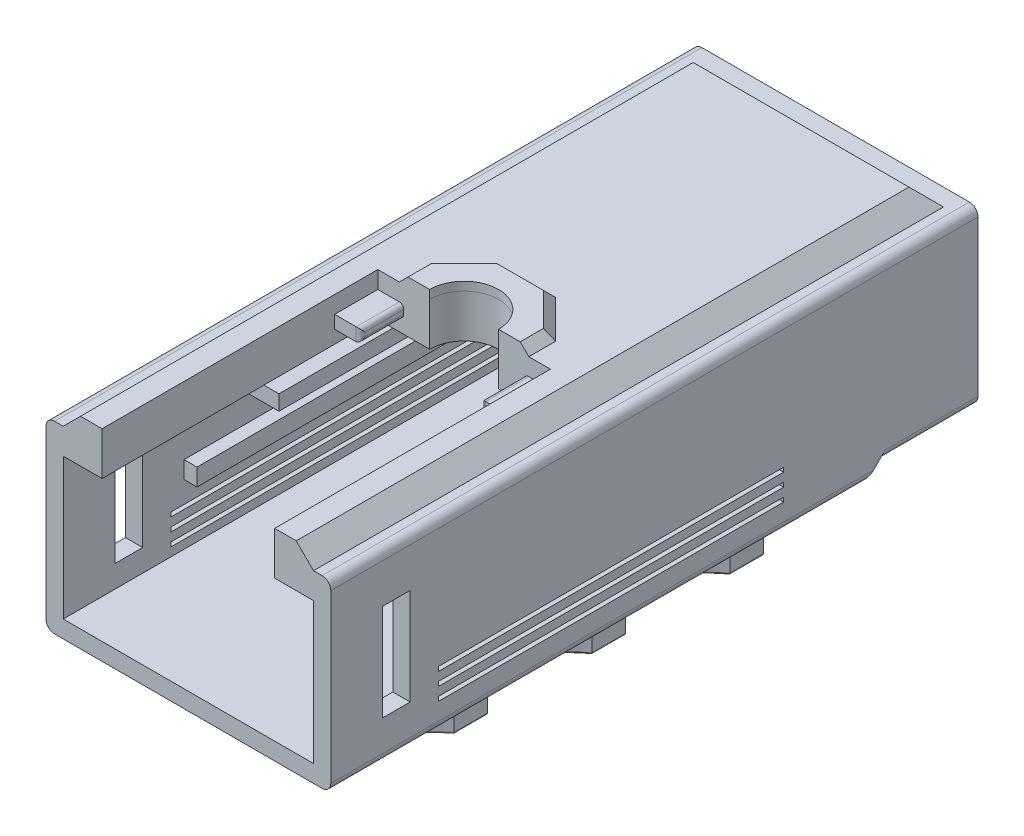
SolidWorks part; units mm, degrees
ref_plane "Front Plane" through (0, 0, 0) normal (0, 0, 1) x (1, 0, 0)
ref_plane "Top Plane" through (0, 0, 0) normal (0, 1, 0) x (1, 0, 0)
ref_plane "Right Plane" through (0, 0, 0) normal (1, 0, 0) x (0, 0, -1)
sketch "Sketch1" plane through (0, 0, 0) normal (0, 0, 1) x (1, 0, 0)
  line L1 (-16.5, 10) -> (16.5, 10)
  line L2 (-16.5, 10) -> (-16.5, -10)
  line L3 (-16.5, -10) -> (16.5, -10)
  line L4 (16.5, 10) -> (16.5, -10)
  line L5 (-16.5, 10) -> (16.5, -10) construction
  line L6 (-16.5, -10) -> (16.5, 10) construction
  point P0 (0, 0)
  dimension "D1" = 33
  dimension "D2" = 20
extrude "Boss-Extrude1" add sketch "Sketch1" along normal blind 70
sketch "Sketch2" plane through (0, 0, 0) normal (0, 0, -1) x (-1, 0, 0)
  line L1 (-16.5, 10) -> (16.5, 10)
  line L2 (-16.5, 10) -> (-16.5, -10)
  line L3 (-16.5, -10) -> (16.5, -10)
  line L4 (16.5, 10) -> (16.5, -10)
  line L5 (-14.5, 7) -> (14.5, 7)
  line L6 (-14.5, 7) -> (-14.5, -7)
  line L7 (-14.5, -7) -> (14.5, -7)
  line L8 (14.5, 7) -> (14.5, -7)
  dimension "D1" = 3
  dimension "D2" = 2
  dimension "D3" = 3
  dimension "D4" = 2
extrude "Cut-Extrude1" cut sketch "Sketch2" against normal blind 9 contours L8 L5 L6 L7 region at (0, 0, 0)
sketch "Sketch3" plane through (0, 0, 70) normal (0, 0, 1) x (1, 0, 0)
  line L1 (-16.5, 10) -> (16.5, 10)
  line L2 (-16.5, 10) -> (-16.5, -10)
  line L3 (-16.5, -10) -> (16.5, -10)
  line L4 (16.5, 10) -> (16.5, -10)
  line L5 (-14.5, 8) -> (14.5, 8)
  line L6 (-14.5, 8) -> (-14.5, -8)
  line L7 (-14.5, -8) -> (14.5, -8)
  line L8 (14.5, 8) -> (14.5, -8)
  dimension "D1" = 2
  dimension "D2" = 2
  dimension "D3" = 2
  dimension "D4" = 2
extrude "Cut-Extrude2" cut sketch "Sketch3" against normal blind 59 contours L8 L5 L6 L7 region at (0, 0, 70)
sketch "Sketch5" plane through (0, 0, 9) normal (0, 0, -1) x (-1, 0, 0)
  line L0 (-14.5, 7) -> (-8.5, 7)
  line L1 (-8.5, 7) -> (-7.5, 7)
  line L2 (-14.5, 7) -> (14.5, 7) construction
  line L3 (-7.5, 7) -> (-0.5, 7)
  line L4 (-14.5, 7) -> (-14.5, 1)
  line L5 (-0.5, 7) -> (0.5, 7)
  line L6 (-14.5, 7) -> (14.5, 7) construction
  line L7 (0.5, 7) -> (7.5, 7)
  line L8 (7.5, 7) -> (8.5, 7)
  line L9 (8.5, 7) -> (14.5, 7)
  line L11 (-14.5, 7) -> (-14.5, -7) construction
  line L12 (14.5, 7) -> (14.5, -7) construction
  line L13 (8.5, -7) -> (14.5, -7)
  line L14 (7.5, -7) -> (8.5, -7)
  line L15 (0.5, -7) -> (7.5, -7)
  line L16 (-0.5, -7) -> (0.5, -7)
  line L17 (-7.5, -7) -> (-0.5, -7)
  line L18 (-8.5, -7) -> (-7.5, -7)
  line L19 (-14.5, -7) -> (-8.5, -7)
  line L20 (-14.5, 7) -> (-14.5, -7) construction
  line L21 (-14.5, -7) -> (-14.5, 0)
  line L22 (-14.5, 1) -> (-14.5, 0)
  line L23 (14.5, -7) -> (14.5, 0)
  line L24 (14.5, 7) -> (14.5, 1)
  line L25 (14.5, 1) -> (14.5, 0)
  line L26 (14.5, 1) -> (14.5, 0)
  line L27 (-8.5, 7) -> (-8.5, 5.2)
  line L28 (-8.5, 5.2) -> (-7.5, 5.2)
  line L29 (-7.5, 5.2) -> (-7.5, 7)
  line L30 (-14.5, 1) -> (-12.7, 1)
  line L31 (-12.7, 1) -> (-12.7, 0)
  line L32 (-12.7, 0) -> (-14.5, 0)
  line L33 (-0.5, 7) -> (-0.5, 1)
  line L34 (0.5, -7) -> (0.5, 0)
  line L35 (14.5, 1) -> (12.7, 1)
  line L36 (12.7, 1) -> (12.7, 0)
  line L37 (12.7, 0) -> (14.5, 0)
  line L38 (8.5, -7) -> (8.5, -4.2)
  line L39 (8.5, -4.2) -> (7.5, -4.2)
  line L40 (7.5, -4.2) -> (7.5, -7)
  line L41 (-7.5, -7) -> (-7.5, -4.2)
  line L42 (-7.5, -4.2) -> (-8.5, -4.2)
  line L43 (-8.5, -4.2) -> (-8.5, -7)
  line L44 (-0.5, 1) -> (-3.2992, 1)
  line L45 (-3.2992, 1) -> (-3.2992, 0)
  line L46 (-3.2992, 0) -> (-0.5, 0)
  line L47 (0.5, 1) -> (3.3, 1)
  line L48 (3.3, 1) -> (3.3, 0)
  line L49 (3.3, 0) -> (0.5, 0)
  line L50 (7.5, 7) -> (7.5, 5.2)
  line L51 (7.5, 5.2) -> (8.5, 5.2)
  line L52 (8.5, 5.2) -> (8.5, 7)
  line L53 (-0.5, 1) -> (0.5, 1)
  line L54 (-0.5, 0) -> (0.5, 0)
  line L55 (-0.5, 0) -> (-0.5, -7)
  line L56 (0.5, 1) -> (0.5, 7)
  line M8 (14.5, -7) -> (14.5, 7)
  line M9 (14.5, 7) -> (-14.5, 7)
  line M10 (-14.5, 7) -> (-14.5, -7)
  line M11 (-14.5, -7) -> (14.5, -7)
extrude "Boss-Extrude2" add sketch "Sketch5" along normal blind 9 contours L51 L52 L50 M9 | L36 L37 L35 M8 | L39 L40 L38 M11 | L28 L29 L27 M9 | L32 L31 L30 M10 | L42 L43 L41 M11 | L49 L48 L47 L34 region at (8, 6.1, 9) region at (13.6, 0.5, 9) region at (-0.0004, 0.5, 9) region at (8, -5.6, 9) region at (-8, 6.1, 9) region at (-13.6, 0.5, 9) region at (-8, -5.6, 9)
extrude "Boss-Extrude3" add sketch "Sketch5<4>" along normal blind 8 contours L54 L55 L34 M11 | L53 L56 L33 M9 region at (0, 4, 9) region at (0, -3.5, 9)
sketch "Sketch5<4>" plane through (0, 0, 9) normal (0, 0, -1) x (-1, 0, 0) same geometry as "Sketch5"
fillet "Fillet1" radius 1 8 edges at (3.2992, 0.5, 0) (-3.3, 0.5, 0) (-8, 5.2, 0) (-12.7, 0.5, 0) (-8, -4.2, 0) (8, -4.2, 0) (12.7, 0.5, 0) (8, 5.2, 0)
sketch "Sketch6" plane through (0, 0, 70) normal (0, 0, 1) x (1, 0, 0)
  line L1 (-16.5, 10) -> (16.5, 10)
  line L2 (-16.5, 10) -> (-16.5, -10)
  line L3 (-16.5, -10) -> (16.5, -10)
  line L4 (16.5, 10) -> (16.5, -10)
  line L5 (-14.5, 8) -> (14.5, 8)
  line L6 (-14.5, 8) -> (-14.5, -8)
  line L7 (-14.5, -8) -> (14.5, -8)
  line L8 (14.5, 8) -> (14.5, -8)
extrude "Cut-Extrude3" cut sketch "Sketch6" against normal blind 19
sketch "Sketch9" plane through (0, 10, 0) normal (0, 1, 0) x (1, 0, 0)
  line L10 (-10, -43.05) -> (-10, -51)
  line L11 (-10, -51) -> (10, -51)
  line L12 (10, -51) -> (10, -43.05)
  line L13 (-4, -43.05) -> (-10, -43.05)
  line L14 (4, -43.05) -> (10, -43.05)
  arc A2 (4, -43.05) -> (-4, -43.05) centre (0, -43.05) ccw
extrude "Cut-Extrude5" cut sketch "Sketch9" against normal blind 2
sketch "Sketch10" plane through (0, 10, 0) normal (0, 1, 0) x (1, 0, 0)
  line L0 (16.5, -51) -> (16.5, 0) construction
  line L1 (-14.5, -2) -> (14.5, -2)
  line L2 (-14.5, -2) -> (-14.5, -42.9994)
  line L4 (14.5, -2) -> (14.5, -42.9994)
  line L5 (-16.5, -51) -> (-16.5, 0) construction
  line L7 (-14.5, -42.9994) -> (-14.5, -51)
  line L8 (-10, -51) -> (-16.5, -51) construction
  line L9 (-14.5, -51) -> (-10, -51)
  line L10 (-10, -51) -> (-10, -43.05)
  line L11 (-10, -43.05) -> (10, -43.05)
  line L12 (10, -43.05) -> (10, -51)
  line L13 (10, -51) -> (14.5, -51)
  line L14 (16.5, -51) -> (10, -51) construction
  line L15 (14.5, -51) -> (14.5, -42.9994)
  arc A0 (4, -42.9994) -> (-4, -42.9994) centre (0, -42.9994) ccw
  dimension "D4" = 8
  dimension "D1" = 2
  dimension "D2" = 2
  dimension "D3" = 2
extrude "Boss-Extrude4" add sketch "Sketch10" along normal blind 2 contours L15 L4 L1 L2 L7 region at (0, 10, 23.5597)
sketch "Sketch11" plane through (0, 8, 0) normal (0, -1, 0) x (1, 0, 0)
  line L0 (14.5, 43.05) -> (14.5, 51)
  line L1 (14.5, 51) -> (10, 51)
  line L2 (0, 31.55) -> (-14.5, 31.55)
  line L4 (-4, 43.05) -> (-10, 43.05)
  line L5 (-14.5, 31.55) -> (-14.5, 43.05)
  line L6 (0, 31.55) -> (14.5, 31.55)
  line L8 (4, 43.05) -> (10, 43.05)
  line L9 (14.5, 31.55) -> (14.5, 43.05)
  line L10 (14.5, 51) -> (10, 51) construction
  line L11 (10, 51) -> (10, 43.05)
  line L12 (-10, 43.05) -> (-10, 51)
  line L13 (-10, 51) -> (-14.5, 51)
  line L14 (-14.5, 51) -> (-14.5, 43.05)
  arc A1 (-4, 43.05) -> (4, 43.05) centre (0, 43.05) ccw
  dimension "D4" = 8
  dimension "D1" = 11.5
  dimension "D2" = 14.5
  dimension "D3" = 14.5
extrude "Boss-Extrude5" add sketch "Sketch11" along normal blind 1
sketch "Sketch13" plane through (14.5, 0, 0) normal (-1, 0, 0) x (0, 0, 1)
  line L1 (31.55, 4.75) -> (51, 4.75)
  line L2 (51, -8) -> (51, 7) construction
  line L7 (51, 4.75) -> (31.55, 4.75)
  line L8 (51, 4.75) -> (51, 3)
  line L9 (51, 3) -> (31.55, 3)
  line L10 (31.55, 4.75) -> (31.55, 3)
  line L11 (51, 4.75) -> (51, 7)
  line L12 (51, 7) -> (31.55, 7)
  line L13 (31.55, 7) -> (31.55, 4.75)
  line M4 (51, 7) -> (31.55, 7)
  line M9 (51, -8) -> (51, 7)
  dimension "D3" = 1.75
extrude "Boss-Extrude6" add sketch "Sketch13" along normal blind 6 contours L1 L10 L9 M9 region at (14.5, 3.875, 41.275)
extrude "Boss-Extrude7" add sketch "Sketch13<5>" along normal blind 4.5 contours L13 L1 M4 M9 region at (14.5, 5.875, 41.275)
sketch "Sketch13<5>" plane through (14.5, 0, 0) normal (-1, 0, 0) x (0, 0, 1) same geometry as "Sketch13"
sketch "Sketch14" plane through (-14.5, 0, 0) normal (1, 0, 0) x (0, 0, -1)
  line L6 (-31.55, 7) -> (-51, 7)
  line L7 (-51, 7) -> (-51, 4.75)
  line L8 (-51, 7) -> (-51, -8) construction
  line L9 (-51, 4.75) -> (-31.55, 4.75)
  line L10 (-31.55, 4.75) -> (-31.55, 7)
  line L11 (-31.55, 4.75) -> (-31.55, 3)
  line L12 (-31.55, 3) -> (-51, 3)
  line L13 (-51, 3) -> (-51, 4.75)
  line M5 (-31.55, 7) -> (-51, 7)
  line M6 (-51, 7) -> (-51, -8)
  dimension "D1" = 2.25
  dimension "D2" = 1.75
extrude "Boss-Extrude8" add sketch "Sketch14" along normal blind 4 contours L12 L11 L9 M6 region at (-14.5, 3.875, 41.275)
extrude "Boss-Extrude9" add sketch "Sketch14<3>" along normal blind 1.75 contours L9 L10 M5 M6 region at (-14.5, 5.875, 41.275)
sketch "Sketch14<3>" plane through (-14.5, 0, 0) normal (1, 0, 0) x (0, 0, -1) same geometry as "Sketch14"
sketch "Sketch18" plane through (14.5, 0, 0) normal (-1, 0, 0) x (0, 0, 1)
  line L4 (51, -8) -> (51, 3) construction
  line L8 (51, -0.35) -> (51, -2.35)
  line L11 (51, -0.35) -> (21, -0.35)
  line L12 (51, -0.35) -> (51, -2.35)
  line L13 (51, -2.35) -> (21, -2.35)
  line L14 (21, -0.35) -> (21, -2.35)
  line M9 (51, -8) -> (51, 3)
  dimension "D1" = 30
  dimension "D2" = 2
extrude "Boss-Extrude11" add sketch "Sketch18" along normal blind 1.5 contours L11 L14 L13 M9 region at (14.5, -1.35, 36)
sketch "Sketch19" plane through (-14.5, 0, 0) normal (1, 0, 0) x (0, 0, -1)
  line L0 (-51, 3) -> (-51, -0.35)
  line L1 (-51, 3) -> (-51, -8) construction
  line L3 (-51, -0.35) -> (-21, -0.35)
  line L4 (-51, -0.35) -> (-51, -2.35)
  line L5 (-51, -2.35) -> (-21, -2.35)
  line L6 (-21, -0.35) -> (-21, -2.35)
  line M7 (-51, 3) -> (-51, -8)
  dimension "D1" = 3.35
  dimension "D2" = 2
  dimension "D3" = 30
extrude "Boss-Extrude12" add sketch "Sketch19" along normal blind 1.5 contours L6 L3 L5 M7 region at (-14.5, -1.35, 36)
sketch "Sketch20" plane through (0, 0, 51) normal (0, 0, 1) x (1, 0, 0)
  line L1 (-14.5, 3) -> (14.5, 3)
  line L2 (-14.5, 3) -> (-14.5, -0.35)
  line L3 (-14.5, -0.35) -> (14.5, -0.35)
  line L4 (14.5, 3) -> (14.5, -0.35)
extrude "Boss-Extrude14" add sketch "Sketch20" against normal blind 2 from offset 30 separate body offset against normal yes
sketch "Sketch21" plane through (-14.5, 0, 0) normal (1, 0, 0) x (0, 0, -1)
  circle A0 centre (-16, -3) radius 2.5
  dimension "D3" = 5
extrude "Cut-Extrude7" cut sketch "Sketch21" against normal through all
sketch "Sketch23" plane through (0, 0, 51) normal (0, 0, 1) x (1, 0, 0)
  line L1 (10, 4.75) -> (-12.75, 4.75)
  line L2 (10, 4.75) -> (10, 7)
  line L3 (10, 7) -> (-12.75, 7)
  line L4 (-12.75, 4.75) -> (-12.75, 7)
extrude "Boss-Extrude15" add sketch "Sketch23" along normal blind 2 from offset 19.95 separate body offset against normal yes
sketch "Sketch24" plane through (0, -8, 0) normal (0, 1, 0) x (1, 0, 0)
  line L0 (-14.5, -2) -> (-14.5, -51) construction
  line L1 (-14.5, -11.1047) -> (14.5, -11.1047)
  line L2 (-14.5, -11.1047) -> (-14.5, -51)
  line L3 (-14.5, -51) -> (14.5, -51)
  line L4 (14.5, -11.1047) -> (14.5, -51)
extrude "Cut-Extrude8" cut sketch "Sketch24" against normal through all
sketch "Sketch25" plane through (14.5, 0, 0) normal (-1, 0, 0) x (0, 0, 1)
  line L1 (51, -10) -> (51, -2.35) construction
  line L2 (51, -9.35) -> (11.1047, -9.35)
  line L3 (11.1047, -10) -> (11.1047, -8) construction
  line L6 (51, -9.35) -> (51, -10)
  line L7 (51, -10) -> (11.1047, -10)
  line L8 (11.1047, -10) -> (11.1047, -9.35)
extrude "Cut-Extrude9" cut sketch "Sketch25" against normal through all
sketch "Sketch26" plane through (-14.5, 0, 0) normal (1, 0, 0) x (0, 0, -1)
  line L1 (-51, -2.35) -> (-51, -10) construction
  line L2 (-11.1047, -10) -> (-11.1047, -8) construction
  line L3 (-51, -9.35) -> (-11.1047, -9.35)
  line L4 (-51, -9.35) -> (-51, -10)
  line L5 (-51, -10) -> (-11.1047, -10)
  line L6 (-11.1047, -9.35) -> (-11.1047, -10)
  line L7 (-11.1047, -10) -> (-51, -10) construction
extrude "Cut-Extrude10" cut sketch "Sketch26" against normal through all
sketch "Sketch27" plane through (0, -9.35, 0) normal (0, -1, 0) x (1, 0, 0)
  line L1 (-16.5, 51) -> (16.5, 51)
  line L2 (-16.5, 51) -> (-16.5, 11.1047)
  line L3 (-16.5, 11.1047) -> (16.5, 11.1047)
  line L4 (16.5, 51) -> (16.5, 11.1047)
extrude "Boss-Extrude16" add sketch "Sketch27" along normal blind 2
sketch "Sketch31" plane through (0, 0, 51) normal (0, 0, 1) x (1, 0, 0)
  line L7 (13.5, -0.35) -> (13, -0.35)
  line L9 (13, -0.35) -> (13, -2.35)
  line L14 (13, -2.35) -> (13.5, -2.3419)
  line L17 (14.5, -0.35) -> (13.5, -0.35)
  line L18 (13, -0.35) -> (14.5, -0.35) construction
  line L20 (13.5, -2.3419) -> (14.5, -2.35)
  line L21 (13, -2.35) -> (14.5, -2.35) construction
  line L22 (14.5, -9.35) -> (14.5, -2.35) construction
  line L26 (-14.5, -2.35) -> (-13, -2.35)
  line L27 (-13, -2.35) -> (-14.5, -2.35) construction
  line L28 (-13, -2.35) -> (-13, -0.35)
  line L29 (-13, -0.35) -> (-13, -2.35) construction
  line L30 (-13, -0.35) -> (-14.5, -0.35)
  line L44 (14.5, -0.35) -> (14.5, -2.35)
  line L45 (-14.5, -0.35) -> (-14.5, -2.35)
  line M4 (-14.5, -2.35) -> (-13, -2.35)
  line M5 (-13, -2.35) -> (-13, -0.35)
  line M6 (-13, -0.35) -> (-14.5, -0.35)
  line M28 (14.5, -0.35) -> (13, -0.35)
  line M29 (13, -0.35) -> (13, -2.35)
extrude "Boss-Extrude18" add sketch "Sketch31" along normal blind 10 contours L45 M6 M4 M5 | L44 L20 M28 M29 region at (13.7502, -1.348, 51) region at (-13.75, -1.35, 51)
sketch "Sketch35" plane through (0, 0, 51) normal (0, 0, 1) x (1, 0, 0)
  line L1 (8.5, 3) -> (14.5, 3) construction
  line L2 (10, 3) -> (8.5, 3)
  line L3 (8.5, 3) -> (8.5, 4.75)
  line L4 (8.5, 3) -> (8.5, 4.75) construction
  line L5 (8.5, 4.75) -> (10, 4.75)
  line L6 (-12.75, 4.75) -> (-10.5, 4.75)
  line L7 (-10.5, 4.75) -> (-12.75, 4.75) construction
  line L8 (-10.5, 4.75) -> (-10.5, 3)
  line L10 (-10.5, 3) -> (-14.5, 3) construction
  line L11 (-12.75, 3) -> (-10.5, 3)
  line L12 (-14.5, 3) -> (-14.5, 4.75)
  line L14 (-12.75, 3) -> (-14.5, 3)
  line L15 (-12.75, 7) -> (-14.5, 7)
  line L16 (-14.5, 7) -> (-14.5, 4.75)
  line L17 (-12.75, 7) -> (-12.75, 4.75)
  line L18 (14.5, 3) -> (10, 3)
  line L19 (14.5, -0.35) -> (14.5, 3) construction
  line L20 (14.5, 3) -> (14.5, 4.75)
  line L22 (14.5, 4.75) -> (14.5, 7)
  line L23 (14.5, 7) -> (10, 7)
  line L24 (10, 4.75) -> (10, 12) construction
  line L25 (10, 7) -> (10, 4.75)
extrude "Boss-Extrude19" add sketch "Sketch35" along normal blind 3
sketch "Sketch36" plane through (0, 0, 51) normal (0, 0, 1) x (1, 0, 0)
  line L0 (-10, 12) -> (-14.5, 12)
  line L1 (-14.5, 12) -> (-10, 12) construction
  line L2 (-14.5, 12) -> (-14.5, 10) construction
  line L3 (-14.5, 12) -> (-14.5, 10)
  line L4 (-14.5, 10) -> (-16.5, 10)
  line L5 (-16.5, 10) -> (-16.5, -11.35)
  line L6 (-16.5, -11.35) -> (16.5, -11.35)
  line L7 (16.5, -11.35) -> (16.5, 10)
  line L8 (16.5, 10) -> (14.5, 10)
  line L9 (14.5, 10) -> (14.5, 12)
  line L10 (14.5, 12) -> (10, 12)
  line L11 (10, 12) -> (14.5, 12) construction
  line L14 (14.5, 3) -> (14.5, -9.35)
  line L15 (14.5, -9.35) -> (-14.5, -9.35)
  line L16 (-14.5, -9.35) -> (-14.5, 3)
  line L19 (-12.75, 7) -> (-10, 7)
  line L20 (-10, 7) -> (-10, 12)
  line L21 (-12.75, 7) -> (-14.5, 7)
  line L22 (-14.5, 7) -> (-14.5, 3)
  line L23 (10, 12) -> (10, 7)
  line L24 (10, 7) -> (10, 12) construction
  line L25 (10, 7) -> (14.5, 7)
  line L26 (14.5, 7) -> (14.5, 3)
extrude "Boss-Extrude20" add sketch "Sketch36" along normal blind 24
sketch "Sketch37" plane through (0, 12, 0) normal (0, 1, 0) x (1, 0, 0)
  line L0 (-7.5, -39.9434) -> (-7.5, -43.05)
  line L3 (7.5, -43.05) -> (7.5, -39.9434)
  line L4 (7.5, -39.9434) -> (3.1066, -35.55)
  line L5 (3.1066, -35.55) -> (-3.1066, -35.55)
  line L6 (-3.1066, -35.55) -> (-7.5, -39.9434)
  line L8 (-7.5, -43.05) -> (-4, -43.05)
  line L9 (3.9927, -43.05) -> (7.5, -43.05)
  line L10 (-3.1066, -50.55) -> (3.1066, -50.55) [skipped]
  line L11 (-7.5, -46.1566) -> (-3.1066, -50.55) [skipped]
  line L12 (3.1066, -50.55) -> (7.5, -46.1566) [skipped]
  arc A0 (-4, -43.05) -> (3.9927, -43.05) centre (-0.0037, -43.05) cw
extrude "Boss-Extrude21" add sketch "Sketch37" along normal blind 1
chamfer "Chamfer3" distance 2 angle 45 4 edges at (0, -11.35, 11.1047) (-14.5, 12, 38.5) (0, 12, 2) (14.5, 12, 38.5)
chamfer "Chamfer4" distance 1 angle 45 5 edges at (7.5, 13, 41.4967) (5.3033, 13, 37.7467) (0, 13, 35.55) (-5.3033, 13, 37.7467) (-7.5, 13, 41.4967)
sketch "Sketch39" plane through (-14.5, 0, 0) normal (1, 0, 0) x (0, 0, -1)
  line L4 (-69, -1.175) -> (-69, 4.425)
  line L5 (-69, 4.425) -> (-65.8, 4.425)
  line L6 (-65.8, -1.175) -> (-65.8, 4.425)
  line L8 (-69, -1.175) -> (-69, -6.775)
  line L9 (-69, -6.775) -> (-65.8, -6.775)
  line L10 (-65.8, -1.175) -> (-65.8, -6.775)
  dimension "D2" = 3.2
  dimension "D3" = 5.6
  dimension "D4" = 5.6
extrude "Cut-Extrude11" cut sketch "Sketch39" against normal through all
sketch "Sketch40" plane through (14.5, 0, 0) normal (-1, 0, 0) x (0, 0, 1)
  line L4 (69, -1.175) -> (69, 4.425)
  line L5 (69, 4.425) -> (65.8, 4.425)
  line L6 (65.8, -1.175) -> (65.8, 4.425)
  line L8 (69, -1.175) -> (69, -6.775)
  line L9 (69, -6.775) -> (65.8, -6.775)
  line L10 (65.8, -1.175) -> (65.8, -6.775)
  dimension "D2" = 3.2
  dimension "D3" = 5.6
  dimension "D4" = 5.6
extrude "Cut-Extrude12" cut sketch "Sketch40" against normal through all
fillet "Fillet2" radius 1 6 edges at (16.5, -11.35, 44.0523) (16.5, -10, 5.8773) (-16.5, -10, 5.8773) (-16.5, -11.35, 44.0523) (-16.5, 10, 37.5) (16.5, 10, 37.5)
sketch "Sketch42" plane through (0, -11.35, 0) normal (0, -1, 0) x (1, 0, 0)
  line L33 (6.5295, 42.534) -> (9.4705, 42.534)
  line L77 (12.7, 53.0532) -> (12.7, 56.9468)
  line L79 (9.9468, 59.7) -> (6.0532, 59.7)
  line L81 (3.3, 56.9468) -> (3.3, 53.0532)
  line L83 (6.0532, 50.3) -> (9.9468, 50.3)
  line L92 (9.4705, 51.45) -> (11.55, 53.5295)
  line L93 (11.55, 53.5295) -> (11.55, 56.4705)
  line L94 (11.55, 56.4705) -> (9.4705, 58.55)
  line L95 (9.4705, 58.55) -> (6.5295, 58.55)
  line L96 (6.5295, 58.55) -> (4.45, 56.4705)
  line L97 (4.45, 56.4705) -> (4.45, 53.5295)
  line L98 (4.45, 53.5295) -> (6.5295, 51.45)
  line L99 (6.5295, 51.45) -> (9.4705, 51.45)
  line L100 (4.45, 40.4544) -> (6.5295, 42.534)
  line L101 (4.45, 37.5135) -> (4.45, 40.4544)
  line L102 (6.5295, 35.434) -> (4.45, 37.5135)
  line L103 (9.4705, 35.434) -> (6.5295, 35.434)
  line L104 (11.55, 37.5135) -> (9.4705, 35.434)
  line L105 (11.55, 40.4544) -> (11.55, 37.5135)
  line L106 (9.4705, 42.534) -> (11.55, 40.4544)
  line L107 (6.0532, 43.684) -> (9.9468, 43.684)
  line L108 (3.3, 37.0372) -> (3.3, 40.9308)
  line L109 (9.9468, 34.284) -> (6.0532, 34.284)
  line L110 (12.7, 40.9308) -> (12.7, 37.0372)
  line L111 (12.7, 21.0692) -> (12.7, 24.9628)
  line L112 (9.9468, 27.716) -> (6.0532, 27.716)
  line L113 (3.3, 24.9628) -> (3.3, 21.0692)
  line L114 (6.0532, 18.316) -> (9.9468, 18.316)
  line L115 (9.4705, 19.466) -> (11.55, 21.5456)
  line L116 (11.55, 21.5456) -> (11.55, 24.4865)
  line L117 (11.55, 24.4865) -> (9.4705, 26.566)
  line L118 (9.4705, 26.566) -> (6.5295, 26.566)
  line L119 (6.5295, 26.566) -> (4.45, 24.4865)
  line L120 (4.45, 24.4865) -> (4.45, 21.5456)
  line L121 (4.45, 21.5456) -> (6.5295, 19.466)
  line L122 (6.5295, 19.466) -> (9.4705, 19.466)
  line L123 (-6.5295, 19.466) -> (-9.4705, 19.466)
  line L124 (-4.45, 21.5456) -> (-6.5295, 19.466)
  line L125 (-4.45, 24.4865) -> (-4.45, 21.5456)
  line L126 (-6.5295, 26.566) -> (-4.45, 24.4865)
  line L127 (-9.4705, 26.566) -> (-6.5295, 26.566)
  line L128 (-11.55, 24.4865) -> (-9.4705, 26.566)
  line L129 (-11.55, 21.5456) -> (-11.55, 24.4865)
  line L130 (-9.4705, 19.466) -> (-11.55, 21.5456)
  line L131 (-6.0532, 18.316) -> (-9.9468, 18.316)
  line L132 (-3.3, 24.9628) -> (-3.3, 21.0692)
  line L133 (-9.9468, 27.716) -> (-6.0532, 27.716)
  line L134 (-12.7, 21.0692) -> (-12.7, 24.9628)
  line L135 (-12.7, 40.9308) -> (-12.7, 37.0372)
  line L136 (-9.9468, 34.284) -> (-6.0532, 34.284)
  line L137 (-3.3, 37.0372) -> (-3.3, 40.9308)
  line L138 (-6.0532, 43.684) -> (-9.9468, 43.684)
  line L139 (-9.4705, 42.534) -> (-11.55, 40.4544)
  line L140 (-11.55, 40.4544) -> (-11.55, 37.5135)
  line L141 (-11.55, 37.5135) -> (-9.4705, 35.434)
  line L142 (-9.4705, 35.434) -> (-6.5295, 35.434)
  line L143 (-6.5295, 35.434) -> (-4.45, 37.5135)
  line L144 (-4.45, 37.5135) -> (-4.45, 40.4544)
  line L145 (-4.45, 40.4544) -> (-6.5295, 42.534)
  line L146 (-6.5295, 42.534) -> (-9.4705, 42.534)
  line L147 (-6.5295, 51.45) -> (-9.4705, 51.45)
  line L148 (-4.45, 53.5295) -> (-6.5295, 51.45)
  line L149 (-4.45, 56.4705) -> (-4.45, 53.5295)
  line L150 (-6.5295, 58.55) -> (-4.45, 56.4705)
  line L151 (-9.4705, 58.55) -> (-6.5295, 58.55)
  line L152 (-11.55, 56.4705) -> (-9.4705, 58.55)
  line L153 (-11.55, 53.5295) -> (-11.55, 56.4705)
  line L154 (-9.4705, 51.45) -> (-11.55, 53.5295)
  line L155 (-6.0532, 50.3) -> (-9.9468, 50.3)
  line L156 (-3.3, 56.9468) -> (-3.3, 53.0532)
  line L157 (-9.9468, 59.7) -> (-6.0532, 59.7)
  line L158 (-12.7, 53.0532) -> (-12.7, 56.9468)
  arc A0 (9.9468, 59.7) -> (12.7, 56.9468) centre (21.8403, 68.8403) ccw
  arc A1 (3.3, 56.9468) -> (6.0532, 59.7) centre (-5.8403, 68.8403) ccw
  arc A2 (3.3, 53.0532) -> (6.0532, 50.3) centre (-5.8403, 41.1597) cw
  arc A3 (9.9468, 50.3) -> (12.7, 53.0532) centre (21.8403, 41.1597) cw
  arc A4 (9.9468, 43.684) -> (12.7, 40.9308) centre (21.8403, 52.8243) ccw
  arc A5 (3.3, 40.9308) -> (6.0532, 43.684) centre (-5.8403, 52.8243) ccw
  arc A6 (3.3, 37.0372) -> (6.0532, 34.284) centre (-5.8403, 25.1437) cw
  arc A7 (9.9468, 34.284) -> (12.7, 37.0372) centre (21.8403, 25.1437) cw
  arc A8 (9.9468, 27.716) -> (12.7, 24.9628) centre (21.8403, 36.8563) ccw
  arc A9 (3.3, 24.9628) -> (6.0532, 27.716) centre (-5.8403, 36.8563) ccw
  arc A10 (3.3, 21.0692) -> (6.0532, 18.316) centre (-5.8403, 9.1757) cw
  arc A11 (9.9468, 18.316) -> (12.7, 21.0692) centre (21.8403, 9.1757) cw
  arc A12 (-9.9468, 18.316) -> (-12.7, 21.0692) centre (-21.8403, 9.1757) ccw
  arc A13 (-3.3, 21.0692) -> (-6.0532, 18.316) centre (5.8403, 9.1757) ccw
  arc A14 (-3.3, 24.9628) -> (-6.0532, 27.716) centre (5.8403, 36.8563) cw
  arc A15 (-9.9468, 27.716) -> (-12.7, 24.9628) centre (-21.8403, 36.8563) cw
  arc A16 (-9.9468, 34.284) -> (-12.7, 37.0372) centre (-21.8403, 25.1437) ccw
  arc A17 (-3.3, 37.0372) -> (-6.0532, 34.284) centre (5.8403, 25.1437) ccw
  arc A18 (-3.3, 40.9308) -> (-6.0532, 43.684) centre (5.8403, 52.8243) cw
  arc A19 (-9.9468, 43.684) -> (-12.7, 40.9308) centre (-21.8403, 52.8243) cw
  arc A20 (-9.9468, 50.3) -> (-12.7, 53.0532) centre (-21.8403, 41.1597) ccw
  arc A21 (-3.3, 53.0532) -> (-6.0532, 50.3) centre (5.8403, 41.1597) ccw
  arc A22 (-3.3, 56.9468) -> (-6.0532, 59.7) centre (5.8403, 68.8403) cw
  arc A23 (-9.9468, 59.7) -> (-12.7, 56.9468) centre (-21.8403, 68.8403) cw
  point P10 (8, 55)
  point P21 (8, 38.984)
  point P46 (8, 23.016)
  point P67 (-8, 23.016)
  point P98 (-8, 38.984)
  point P132 (-8, 55)
  dimension "D1" = 15
  dimension "D2" = 15
  dimension "D3" = 15
  dimension "D4" = 15
extrude "Boss-Extrude23" add sketch "Sketch42" along normal blind 5
fillet "Fillet4" radius 0.2 96 edges at (-4.7663, -16.35, 26.2497) (-8, -16.35, 27.716) (-12.7, -16.35, 23.016) (-11.2337, -16.35, 26.2497) (-3.3, -16.35, 23.016) (-11.2337, -16.35, 19.7823) (-8, -16.35, 18.316) (-4.7663, -16.35, 19.7823) (-8, -16.35, 26.566) (-10.5102, -16.35, 25.5262) (-11.55, -16.35, 23.016) (-10.5102, -16.35, 20.5058) (-8, -16.35, 19.466) (-5.4898, -16.35, 25.5262) (-5.4898, -16.35, 20.5058) (-4.45, -16.35, 23.016) (12.7, -16.35, 23.016) (11.2337, -16.35, 19.7823) (8, -16.35, 18.316) (11.55, -16.35, 23.016) (10.5102, -16.35, 20.5058) (8, -16.35, 19.466) (5.4898, -16.35, 20.5058) (4.45, -16.35, 23.016) (5.4898, -16.35, 25.5262) (8, -16.35, 26.566) (10.5102, -16.35, 25.5262) (11.2337, -16.35, 26.2497) (4.7663, -16.35, 19.7823) (3.3, -16.35, 23.016) (8, -16.35, 27.716) (4.7663, -16.35, 26.2497) (5.4898, -16.35, 36.4738) (11.55, -16.35, 38.984) (8, -16.35, 35.434) (10.5102, -16.35, 36.4738) (11.2337, -16.35, 42.2177) (8, -16.35, 43.684) (4.7663, -16.35, 42.2177) (3.3, -16.35, 38.984) (-4.45, -16.35, 38.984) (-5.4898, -16.35, 36.4738) (-8, -16.35, 35.434) (5.4898, -16.35, 52.4898) (8, -16.35, 51.45) (10.5102, -16.35, 52.4898) (11.55, -16.35, 55) (3.3, -16.35, 55) (4.7663, -16.35, 58.2337) (8, -16.35, 59.7) (11.2337, -16.35, 58.2337) (-4.7663, -16.35, 42.2177) (-8, -16.35, 43.684) (-11.2337, -16.35, 42.2177) (-12.7, -16.35, 38.984) (-11.2337, -16.35, 35.7503) (-10.5102, -16.35, 36.4738) (-11.55, -16.35, 38.984) (10.5102, -16.35, 41.4942) (5.4898, -16.35, 41.4942) (4.45, -16.35, 38.984) (4.7663, -16.35, 35.7503) (8, -16.35, 34.284) (11.2337, -16.35, 35.7503) (12.7, -16.35, 38.984) (8, -16.35, 42.534) (4.45, -16.35, 55) (5.4898, -16.35, 57.5102) (10.5102, -16.35, 57.5102) (8, -16.35, 58.55) (4.7663, -16.35, 51.7663) (12.7, -16.35, 55) (11.2337, -16.35, 51.7663) (8, -16.35, 50.3) (-3.3, -16.35, 38.984) (-4.7663, -16.35, 35.7503) (-8, -16.35, 34.284) (-5.4898, -16.35, 41.4942) (-8, -16.35, 42.534) (-10.5102, -16.35, 41.4942) (-5.4898, -16.35, 57.5102) (-8, -16.35, 58.55) (-10.5102, -16.35, 57.5102) (-11.55, -16.35, 55) (-10.5102, -16.35, 52.4898) (-8, -16.35, 51.45) (-4.45, -16.35, 55) (-5.4898, -16.35, 52.4898) (-11.2337, -16.35, 58.2337) (-12.7, -16.35, 55) (-11.2337, -16.35, 51.7663) (-8, -16.35, 50.3) (-4.7663, -16.35, 51.7663) (-8, -16.35, 59.7) (-4.7663, -16.35, 58.2337) (-3.3, -16.35, 55)
sketch "Sketch43" plane through (-16.5, 0, 0) normal (-1, 0, 0) x (0, 0, 1)
  line L0 (12.1047, -10.35) -> (75, -10.35) construction
  line L1 (22.533, -6.85) -> (62.533, -6.85)
  line L2 (22.533, -6.85) -> (22.533, -6.35)
  line L3 (22.533, -6.35) -> (62.533, -6.35)
  line L4 (62.533, -6.85) -> (62.533, -6.35)
  line L5 (22.533, -7.85) -> (62.533, -7.85)
  line L6 (22.533, -7.85) -> (22.533, -8.35)
  line L7 (22.533, -8.35) -> (62.533, -8.35)
  line L8 (62.533, -7.85) -> (62.533, -8.35)
  line L9 (22.533, -5.35) -> (62.533, -5.35)
  line L10 (22.533, -5.35) -> (22.533, -4.85)
  line L11 (22.533, -4.85) -> (62.533, -4.85)
  line L12 (62.533, -5.35) -> (62.533, -4.85)
  dimension "D1" = 0.5
  dimension "D2" = 0.5
  dimension "D3" = 0.5
  dimension "D4" = 1
  dimension "D5" = 1
  dimension "D6" = 2
  dimension "D7" = 40
  dimension "D8" = 40
  dimension "D9" = 40
extrude "Cut-Extrude14" cut sketch "Sketch43" against normal through all
sketch "Sketch44" plane through (10, 0, 0) normal (-1, 0, 0) x (0, 0, 1)
  line L0 (43.05, 12) -> (43.05, 10)
  line L1 (43.05, 7) -> (43.05, 12) construction
  line L3 (43.05, 10) -> (48.05, 10)
  line L4 (43.05, 10) -> (43.05, 8.5)
  line L5 (43.05, 8.5) -> (48.05, 8.5)
  line L6 (48.05, 10) -> (48.05, 8.5)
  line M6 (43.05, 12) -> (43.05, 7)
  dimension "D1" = 2
  dimension "D2" = 5
  dimension "D3" = 1.5
extrude "Boss-Extrude24" add sketch "Sketch44" along normal blind 3 contours L6 L3 L5 M6 region at (10, 9.25, 45.55)
sketch "Sketch45" plane through (-10, 0, 0) normal (1, 0, 0) x (0, 0, -1)
  line L0 (-43.05, 12) -> (-43.05, 10)
  line L1 (-43.05, 7) -> (-43.05, 12) construction
  line L3 (-43.05, 10) -> (-48.05, 10)
  line L4 (-43.05, 10) -> (-43.05, 8.5)
  line L5 (-43.05, 8.5) -> (-48.05, 8.5)
  line L6 (-48.05, 10) -> (-48.05, 8.5)
  line M4 (-43.05, 7) -> (-43.05, 12)
  dimension "D1" = 2
  dimension "D2" = 5
  dimension "D3" = 1.5
extrude "Boss-Extrude25" add sketch "Sketch45" along normal blind 3 contours L3 L6 L5 M4 region at (-10, 9.25, 45.55)
fillet "Fillet6" radius 0.5 6 edges at (7, 8.5, 45.55) (7, 9.25, 48.05) (7, 10, 45.55) (-7, 9.25, 48.05) (-7, 8.5, 45.55) (-7, 10, 45.55)
